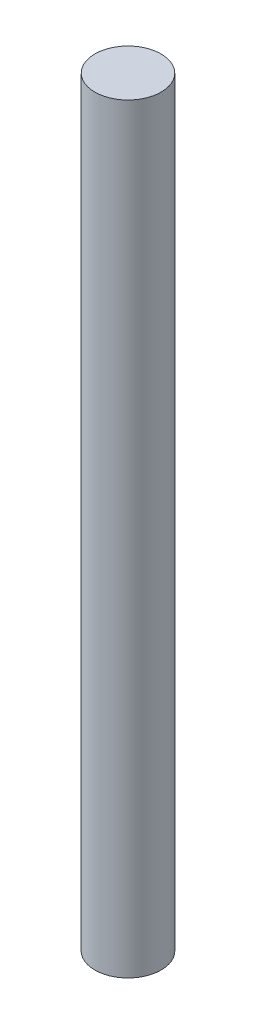
SolidWorks part; units mm, degrees
material "AISI 304"
ref_plane "Front Plane" through (0, 0, 0) normal (0, 0, 1) x (1, 0, 0)
ref_plane "Top Plane" through (0, 0, 0) normal (0, 1, 0) x (1, 0, 0)
ref_plane "Right Plane" through (0, 0, 0) normal (1, 0, 0) x (0, 0, -1)
sketch "Sketch1" plane through (0, 0, 0) normal (0, 1, 0) x (1, 0, 0)
  circle A0 centre (0, 0) radius 4
  dimension "D1" = 8
extrude "Boss-Extrude1" add sketch "Sketch1" along normal mid plane 91.9
